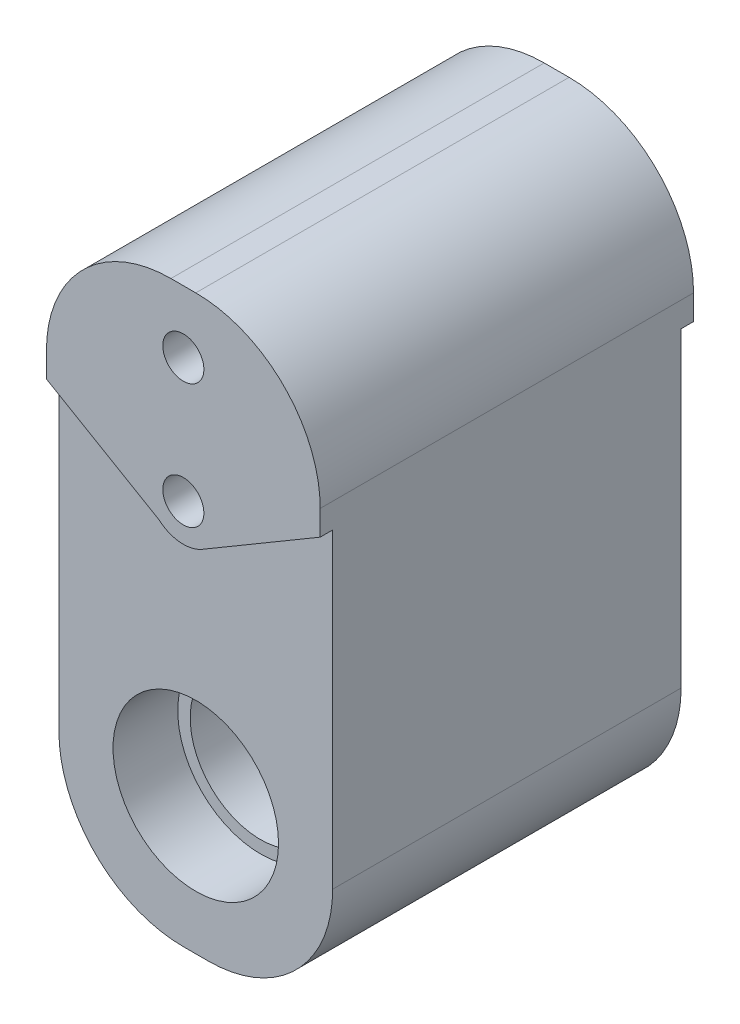
SolidWorks part; units mm, degrees
ref_plane "Спереди" through (0, 0, 0) normal (0, 0, 1) x (1, 0, 0)
ref_plane "Сверху" through (0, 0, 0) normal (0, 1, 0) x (1, 0, 0)
ref_plane "Справа" through (0, 0, 0) normal (1, 0, 0) x (0, 0, -1)
sketch "Эскиз1" plane through (0, 0, 0) normal (0, 0, 1) x (1, 0, 0)
  line L0 (0, 36) -> (0, -11) construction
  line L1 (-11, 36) -> (11, 36)
  line L2 (-11, 36) -> (-11, -11)
  line L3 (-11, -11) -> (11, -11)
  line L4 (11, 36) -> (11, -11)
  line L6 (-11, 0) -> (11, 0) construction
  dimension "D1" = 22
  dimension "D2" = 11
  dimension "D3" = 36
extrude "тело" add sketch "Эскиз1" along normal blind 14 and the other way blind 14
sketch "Эскиз2" plane through (0, 0, 14) normal (0, 0, 1) x (1, 0, 0)
  circle A0 centre (0, 0) radius 6.65
  dimension "D1" = 13.3
extrude "углубление для подшипника" cut sketch "Эскиз2" against normal blind 5.2
sketch "Эскиз4" plane through (0, 0, 8.8) normal (0, 0, 1) x (1, 0, 0)
  line L1 (0, 36) -> (0, -11) construction
  line L2 (-11, 0) -> (11, 0) construction
  circle A0 centre (0, 0) radius 5.65
  circle A1 centre (0, 0) radius 6.65 construction
  dimension "D1" = 1
extrude "сквозное отверстие" cut sketch "Эскиз4" against normal through all
mirror "Зеркальное отражение2" about plane through (0, 0, 0) normal (0, 0, 1) of "углубление для подшипника"
sketch "Эскиз5" plane through (0, 0, -14) normal (0, 0, -1) x (-1, 0, 0)
  line L0 (0, 36) -> (0, -11) construction
  line L1 (-11, 36) -> (11, 36) construction
  line L2 (11, -11) -> (-11, -11) construction
  circle A0 centre (0, 31) radius 1.65
  circle A1 centre (0, 21) radius 1.65
  dimension "D1" = 3.3
  dimension "D2" = 10
  dimension "D3" = 5
extrude "отверстия под болты" cut sketch "Эскиз5" against normal through all
sketch "Эскиз9" plane through (0, 0, 14) normal (0, 0, 1) x (1, 0, 0)
  line L0 (-11, 36) -> (-11, 24)
  line L1 (-11, 36) -> (-11, -11) construction
  line L2 (-11, 36) -> (11, 36)
  line L3 (-11, 24) -> (-1.9948, 18.7593)
  line L4 (11, 36) -> (11, 24)
  line L5 (11, 24) -> (1.5231, 18.4154)
  line L6 (11, -11) -> (11, 36) construction
  arc A0 (-1.9948, 18.7593) -> (1.5231, 18.4154) centre (0, 21) ccw
  circle A1 centre (0, 21) radius 1.65
  circle A2 centre (0, 31) radius 1.65
  circle A3 centre (0, 31) radius 1.65 construction
  circle A4 centre (0, 21) radius 1.65 construction
  dimension "D1" = 6
  dimension "D2" = 12
extrude "выступы" add sketch "Эскиз9" along normal blind 1
mirror "Зеркальное отражение1" about plane through (0, 0, 0) normal (0, 0, 1) of "выступы"
fillet "Скругление1" radius 10 4 edges at (11, -11, 0) (-11, -11, 0) (-11, 36, 0) (11, 36, 0)
